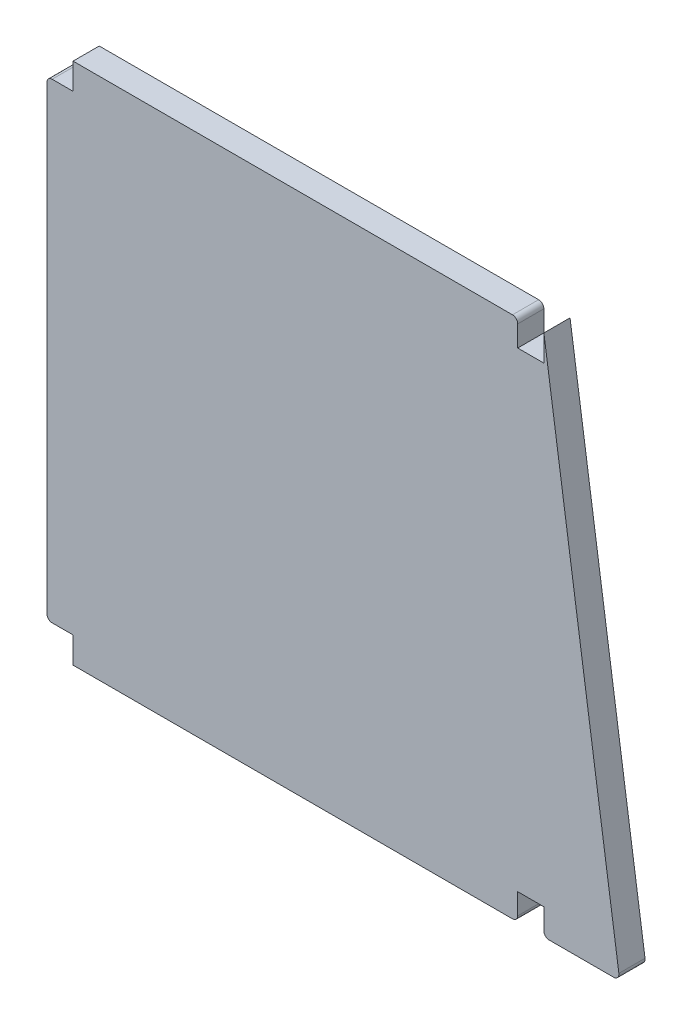
SolidWorks part; units mm, degrees
ref_plane "Front" through (0, 0, 0) normal (0, 0, 1) x (1, 0, 0)
ref_plane "Top" through (0, 0, 0) normal (0, 1, 0) x (1, 0, 0)
ref_plane "Right" through (0, 0, 0) normal (1, 0, 0) x (0, 0, -1)
sketch "Sketch1" plane through (0, 0, 0) normal (0, 0, 1) x (1, 0, 0)
  line L0 (0, 95) -> (0, 100)
  line L1 (0, 0) -> (85, 0)
  line L2 (0, 0) -> (0, 5)
  line L3 (0, 100) -> (85, 100)
  line L4 (85, 0) -> (85, 5)
  line L5 (0, 95) -> (-5, 95)
  line L7 (0, 5) -> (-5, 5)
  line L8 (-5, 95) -> (-5, 5)
  line L9 (85, 95) -> (90, 95)
  line L11 (85, 5) -> (90, 5)
  line L13 (85, 95) -> (85, 100)
  line L14 (90, 5) -> (90, 0)
  line L15 (90, 0) -> (104.5, 0)
  line L16 (104.5, 0) -> (90, 100)
  line L17 (90, 100) -> (90, 95)
  point P13 (-2.5, 95)
  dimension "D1" = 85
  dimension "D2" = 5
  dimension "D3" = 5
  dimension "D4" = 5
  dimension "D5" = 5
  dimension "D6" = 5
  dimension "D7" = 100
  dimension "D8" = 5
  dimension "D9" = 14.5
extrude "Boss-Extrude1" add sketch "Sketch1" along normal blind 5
fillet "Fillet1" radius 1 6 edges at (85, 100, 2.5) (104.5, 0, 2.5) (90, 0, 2.5) (85, 0, 2.5) (-5, 5, 2.5) (-5, 95, 2.5)
